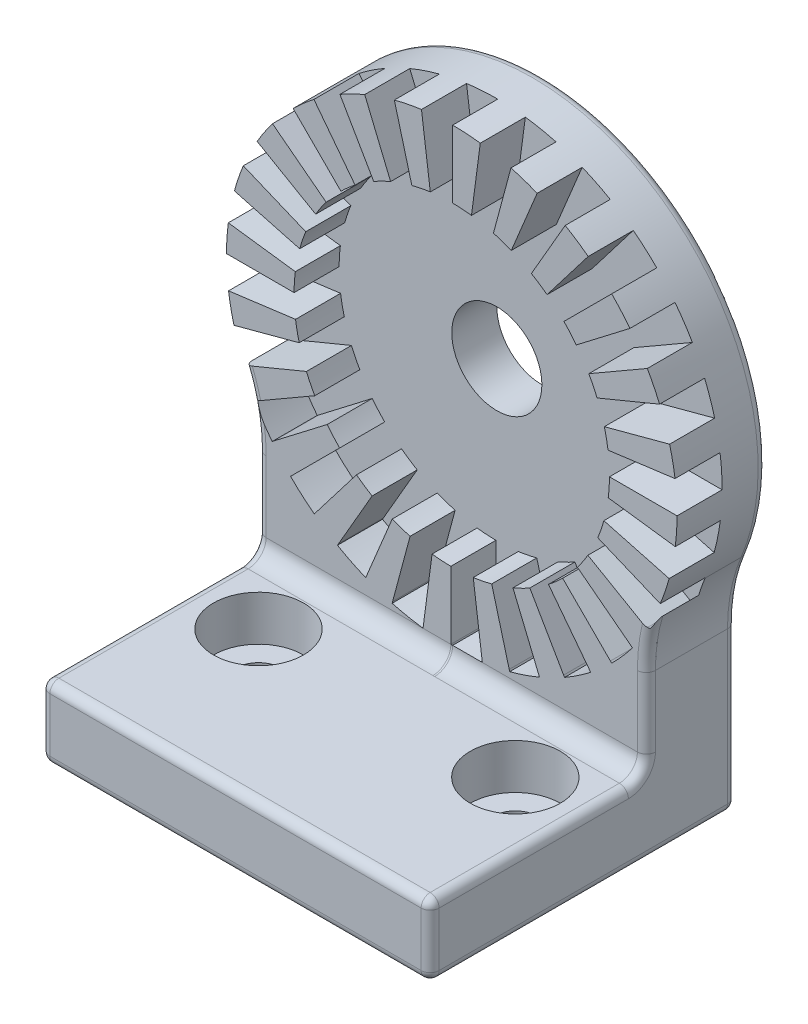
SolidWorks part; units mm, degrees
note: The reader was unsure of these and kept them because the rebuilt part matched: shared geometry of "Sketch1<3>", "Sketch2<3>".
ref_plane "Front Plane" through (0, 0, 0) normal (0, 0, 1) x (1, 0, 0)
ref_plane "Top Plane" through (0, 0, 0) normal (0, 1, 0) x (1, 0, 0)
ref_plane "Right Plane" through (0, 0, 0) normal (1, 0, 0) x (0, 0, -1)
sketch "Sketch1" plane through (0, 0, 0) normal (0, 0, 1) x (1, 0, 0)
  line L0 (0, 0) -> (0, 25) construction
  line L1 (0, 0) -> (3.2632, 24.7861) construction
  line L2 (0, 0) -> (6.4705, 24.1481) construction
  line L3 (0, 0) -> (9.5671, 23.097) construction
  line L4 (0, 0) -> (12.5, 21.6506) construction
  line L5 (0, 0) -> (15.219, 19.8338) construction
  line L6 (0, 0) -> (17.6777, 17.6777) construction
  line L7 (0, 0) -> (19.8338, 15.219) construction
  line L8 (0, 0) -> (21.6506, 12.5) construction
  line L9 (0, 0) -> (23.097, 9.5671) construction
  line L10 (0, 0) -> (24.1481, 6.4705) construction
  line L11 (0, 0) -> (24.7861, 3.2632) construction
  line L12 (0, 0) -> (25, 0) construction
  line L13 (0, 0) -> (24.7861, -3.2632) construction
  line L14 (0, 0) -> (24.1481, -6.4705) construction
  line L15 (0, 0) -> (23.097, -9.5671) construction
  line L16 (0, 0) -> (21.6506, -12.5) construction
  line L17 (0, 0) -> (19.8338, -15.219) construction
  line L18 (0, 0) -> (17.6777, -17.6777) construction
  line L19 (0, 0) -> (15.219, -19.8338) construction
  line L20 (0, 0) -> (12.5, -21.6506) construction
  line L21 (0, 0) -> (9.5671, -23.097) construction
  line L22 (0, 0) -> (6.4705, -24.1481) construction
  line L23 (0, 0) -> (3.2632, -24.7861) construction
  line L24 (0, 0) -> (0, -25) construction
  line L25 (0, 0) -> (-3.2632, -24.7861) construction
  line L26 (0, 0) -> (-6.4705, -24.1481) construction
  line L27 (0, 0) -> (-9.5671, -23.097) construction
  line L28 (0, 0) -> (-12.5, -21.6506) construction
  line L29 (0, 0) -> (-15.219, -19.8338) construction
  line L30 (0, 0) -> (-17.6777, -17.6777) construction
  line L31 (0, 0) -> (-19.8338, -15.219) construction
  line L32 (0, 0) -> (-21.6506, -12.5) construction
  line L33 (0, 0) -> (-23.097, -9.5671) construction
  line L34 (0, 0) -> (-24.1481, -6.4705) construction
  line L35 (0, 0) -> (-24.7861, -3.2632) construction
  line L36 (0, 0) -> (-25, 0) construction
  line L37 (0, 0) -> (-24.7861, 3.2632) construction
  line L38 (0, 0) -> (-24.1481, 6.4705) construction
  line L39 (0, 0) -> (-23.097, 9.5671) construction
  line L40 (0, 0) -> (-21.6506, 12.5) construction
  line L41 (0, 0) -> (-19.8338, 15.219) construction
  line L42 (0, 0) -> (-17.6777, 17.6777) construction
  line L43 (0, 0) -> (-15.219, 19.8338) construction
  line L44 (0, 0) -> (-12.5, 21.6506) construction
  line L45 (0, 0) -> (-9.5671, 23.097) construction
  line L46 (0, 0) -> (-6.4705, 24.1481) construction
  line L47 (0, 0) -> (-3.2632, 24.7861) construction
  line L48 (-1.5257, 0.1) -> (-24.7992, 3.164)
  line L49 (-1.5257, 0.1) -> (-25, 0.1)
  line L50 (-1.4478, 0.4915) -> (-23.1353, 9.4747)
  line L51 (-1.4478, 0.4915) -> (-24.1223, 6.5671)
  line L52 (-1.2713, 0.8495) -> (-19.8947, 15.1397)
  line L53 (-1.2713, 0.8495) -> (-21.6006, 12.5866)
  line L54 (-1.0081, 1.1495) -> (-15.2984, 19.773)
  line L55 (-1.0081, 1.1495) -> (-17.607, 17.7484)
  line L56 (-0.6763, 1.3713) -> (-9.6595, 23.0587)
  line L57 (-0.6763, 1.3713) -> (-12.4134, 21.7006)
  line L58 (-0.2983, 1.4996) -> (-3.3623, 24.7731)
  line L59 (-0.2983, 1.4996) -> (-6.3739, 24.174)
  line L60 (0.1, 1.5257) -> (3.164, 24.7992)
  line L61 (0.1, 1.5257) -> (0.1, 25)
  line L62 (0.4915, 1.4478) -> (9.4747, 23.1353)
  line L63 (0.4915, 1.4478) -> (6.5671, 24.1223)
  line L64 (0.8495, 1.2713) -> (15.1397, 19.8947)
  line L65 (0.8495, 1.2713) -> (12.5866, 21.6006)
  line L66 (1.1495, 1.0081) -> (19.773, 15.2984)
  line L67 (1.1495, 1.0081) -> (17.7484, 17.607)
  line L68 (1.3713, 0.6763) -> (23.0587, 9.6595)
  line L69 (1.3713, 0.6763) -> (21.7006, 12.4134)
  line L70 (1.4996, 0.2983) -> (24.7731, 3.3623)
  line L71 (1.4996, 0.2983) -> (24.174, 6.3739)
  line L72 (1.5257, -0.1) -> (24.7992, -3.164)
  line L73 (1.5257, -0.1) -> (25, -0.1)
  line L74 (1.4478, -0.4915) -> (23.1353, -9.4747)
  line L75 (1.4478, -0.4915) -> (24.1223, -6.5671)
  line L76 (1.2713, -0.8495) -> (19.8947, -15.1397)
  line L77 (1.2713, -0.8495) -> (21.6006, -12.5866)
  line L78 (1.0081, -1.1495) -> (15.2984, -19.773)
  line L79 (1.0081, -1.1495) -> (17.607, -17.7484)
  line L80 (0.6763, -1.3713) -> (9.6595, -23.0587)
  line L81 (0.6763, -1.3713) -> (12.4134, -21.7006)
  line L82 (0.2983, -1.4996) -> (3.3623, -24.7731)
  line L83 (0.2983, -1.4996) -> (6.3739, -24.174)
  line L84 (-0.1, -1.5257) -> (-3.164, -24.7992)
  line L85 (-0.1, -1.5257) -> (-0.1, -25)
  line L86 (-0.4915, -1.4478) -> (-9.4747, -23.1353)
  line L87 (-0.4915, -1.4478) -> (-6.5671, -24.1223)
  line L88 (-0.8495, -1.2713) -> (-15.1397, -19.8947)
  line L89 (-0.8495, -1.2713) -> (-12.5866, -21.6006)
  line L90 (-1.1495, -1.0081) -> (-19.773, -15.2984)
  line L91 (-1.1495, -1.0081) -> (-17.7484, -17.607)
  line L92 (-1.3713, -0.6763) -> (-23.0587, -9.6595)
  line L93 (-1.3713, -0.6763) -> (-21.7006, -12.4134)
  line L94 (-1.4996, -0.2983) -> (-24.7731, -3.3623)
  line L95 (-1.4996, -0.2983) -> (-24.174, -6.3739)
  circle A0 centre (0, 0) radius 25 construction
  arc A1 (-25, 0.1) -> (-24.7992, 3.164) centre (-1.5257, 0.1) cw
  arc A2 (-24.1223, 6.5671) -> (-23.1353, 9.4747) centre (-1.4478, 0.4915) cw
  arc A3 (-21.6006, 12.5866) -> (-19.8947, 15.1397) centre (-1.2713, 0.8495) cw
  arc A4 (-17.607, 17.7484) -> (-15.2984, 19.773) centre (-1.0081, 1.1495) cw
  arc A5 (-12.4134, 21.7006) -> (-9.6595, 23.0587) centre (-0.6763, 1.3713) cw
  arc A6 (-6.3739, 24.174) -> (-3.3623, 24.7731) centre (-0.2983, 1.4996) cw
  arc A7 (0.1, 25) -> (3.164, 24.7992) centre (0.1, 1.5257) cw
  arc A8 (6.5671, 24.1223) -> (9.4747, 23.1353) centre (0.4915, 1.4478) cw
  arc A9 (12.5866, 21.6006) -> (15.1397, 19.8947) centre (0.8495, 1.2713) cw
  arc A10 (17.7484, 17.607) -> (19.773, 15.2984) centre (1.1495, 1.0081) cw
  arc A11 (21.7006, 12.4134) -> (23.0587, 9.6595) centre (1.3713, 0.6763) cw
  arc A12 (24.174, 6.3739) -> (24.7731, 3.3623) centre (1.4996, 0.2983) cw
  arc A13 (25, -0.1) -> (24.7992, -3.164) centre (1.5257, -0.1) cw
  arc A14 (24.1223, -6.5671) -> (23.1353, -9.4747) centre (1.4478, -0.4915) cw
  arc A15 (21.6006, -12.5866) -> (19.8947, -15.1397) centre (1.2713, -0.8495) cw
  arc A16 (17.607, -17.7484) -> (15.2984, -19.773) centre (1.0081, -1.1495) cw
  arc A17 (12.4134, -21.7006) -> (9.6595, -23.0587) centre (0.6763, -1.3713) cw
  arc A18 (6.3739, -24.174) -> (3.3623, -24.7731) centre (0.2983, -1.4996) cw
  arc A19 (-0.1, -25) -> (-3.164, -24.7992) centre (-0.1, -1.5257) cw
  arc A20 (-6.5671, -24.1223) -> (-9.4747, -23.1353) centre (-0.4915, -1.4478) cw
  arc A21 (-12.5866, -21.6006) -> (-15.1397, -19.8947) centre (-0.8495, -1.2713) cw
  arc A22 (-17.7484, -17.607) -> (-19.773, -15.2984) centre (-1.1495, -1.0081) cw
  arc A23 (-21.7006, -12.4134) -> (-23.0587, -9.6595) centre (-1.3713, -0.6763) cw
  arc A24 (-24.174, -6.3739) -> (-24.7731, -3.3623) centre (-1.4996, -0.2983) cw
  circle A25 centre (0, 0) radius 25
  point P54 (0, 0)
  point P150 (0, 0)
  dimension "D1" = 50
  dimension "D4" = 24
  dimension "D5" = 50
  dimension "D2" = 48
  dimension "D3" = 0.1
extrude "Boss-Extrude1" add sketch "Sketch1" along normal blind 10 contours L48 A25 L49 | L50 A25 L51 | L52 A25 L53 | L54 A25 L55 | L56 A25 L57 | L58 A25 L59 | L60 A25 L61 | L62 A25 L63 | L64 A25 L65 | L66 A25 L67 | L68 A25 L69 | L70 A25 L71 | L72 A25 L73 | L74 A25 L75 | L76 A25 L77 | L78 A25 L79 | L80 A25 L81 | L82 A25 L83 | L86 A25 L87 | L88 A25 L89 | L90 A25 L91 | L92 A25 L93 | L94 A25 L95 | L84 A19 L85
extrude "Boss-Extrude2" add sketch "Sketch1<3>" along normal blind 5 contours A25
sketch "Sketch1<3>" plane through (0, 0, 0) normal (0, 0, 1) x (1, 0, 0) same geometry as "Sketch1"
sketch "Sketch2" plane through (0, 0, 0) normal (0, 0, 1) x (1, 0, 0)
  circle A0 centre (0, 0) radius 5
  circle A1 centre (0, 0) radius 17.5
  dimension "D1" = 10
  dimension "D2" = 35
extrude "Cut-Extrude1" cut sketch "Sketch2" along normal through all contours A0
extrude "Boss-Extrude3" add sketch "Sketch2<3>" along normal through all
sketch "Sketch2<3>" plane through (0, 0, 0) normal (0, 0, 1) x (1, 0, 0) same geometry as "Sketch2"
sketch "Sketch3" plane through (0, 0, 0) normal (0, 0, 1) x (1, 0, 0)
  line L0 (21.6005, -12.5865) -> (21.6005, -35)
  line L1 (21.6005, -35) -> (-21.6005, -35)
  line L2 (-21.6005, -35) -> (-21.6005, -12.5865)
  arc A1 (-24.799, 3.164) -> (-24.9998, 0.1) centre (0, 0) ccw construction
  arc A5 (-21.6005, -12.5865) -> (21.6005, -12.5865) centre (0, 0) ccw
  dimension "D1" = 10
extrude "Boss-Extrude4" add sketch "Sketch3" along normal blind 10 contours A5 L2 L1 L0
fillet "Fillet1" radius 20 2 edges at (21.6005, -12.5865, 2.5) (-21.6005, -12.5865, 2.5)
sketch "Sketch4" plane through (0, 0, 0) normal (0, 0, 1) x (1, 0, 0)
  line L0 (-22.1146, -12.6524) -> (-15.2052, -8.6633) construction
  line L1 (-21.6005, -35) -> (-21.6005, -12.5865) construction
  line L2 (-22.1146, -12.6524) -> (-21.7071, -12.4172)
  line L3 (-21.6005, -35) -> (-21.6005, -12.5865)
  line L4 (-21.7071, -12.4172) -> (-15.2052, -8.6633) construction
  arc A0 (-21.6005, -12.5865) -> (-19.7728, -15.2982) centre (0, 0) ccw construction
  arc A1 (-21.6005, -12.5865) -> (-19.7728, -15.2982) centre (0, 0) ccw construction
  arc A2 (-21.6005, -12.5865) -> (-21.7071, -12.4172) centre (-24.1024, -14.0444) ccw
  arc A3 (-21.6005, -17.1581) -> (-22.1146, -12.6524) centre (-41.6005, -17.1581) ccw construction
  arc A4 (-21.6005, -17.1581) -> (-22.1146, -12.6524) centre (-41.6005, -17.1581) ccw
extrude "Boss-Extrude5" add sketch "Sketch4" along normal blind 10 contours A4 L3 A2 L2
sketch "Sketch5" plane through (0, 0, 0) normal (0, 0, 1) x (1, 0, 0)
  line L0 (21.6005, -12.5865) -> (21.6005, -35) construction
  line L1 (21.6005, -12.5865) -> (21.6005, -17.1581)
  line L2 (21.6005, -17.1581) -> (21.6005, -35) construction
  arc A0 (23.1114, -9.5323) -> (21.6005, -17.1581) centre (41.6005, -17.1581) ccw construction
  arc A1 (23.1114, -9.5323) -> (21.6005, -17.1581) centre (41.6005, -17.1581) ccw
  arc A2 (23.1114, -9.5323) -> (21.6005, -12.5865) centre (0, 0) cw
extrude "Boss-Extrude6" add sketch "Sketch5" along normal blind 10
sketch "Sketch6" plane through (0, 0, 0) normal (0, 0, 1) x (1, 0, 0)
  line L0 (21.6005, -17.1581) -> (21.6005, -35) construction
  line L1 (-21.6005, -35) -> (21.6005, -35)
  line L2 (-21.6005, -35) -> (-21.6005, -26.9998)
  line L3 (-21.6005, -26.9998) -> (21.6005, -26.9998)
  line L4 (21.6005, -35) -> (21.6005, -26.9998)
  dimension "D1" = 2
extrude "Boss-Extrude7" add sketch "Sketch6" along normal blind 34
fillet "Fillet2" radius 2 1 edges at (0, -26.9998, 10)
fillet "Fillet3" radius 1 20 edges at (0, -35, 0) (0, -35, 34) (-21.9686, -13.3386, 10) (-21.6005, -21.079, 10) (-21.6005, -26.414, 10.5858) (21.9818, -13.2711, 10) (21.6005, -21.079, 10) (21.6005, -26.414, 10.5858) (-21.6005, -26.0791, 0) (-21.9818, -13.2711, 0) (0, 25, 0) (21.9818, -13.2711, 0) (-21.6005, -26.9998, 23) (21.6005, -26.9998, 23) (21.6005, -26.0791, 0) (21.6005, -30.9999, 34) (21.6005, -35, 17) (-21.6005, -35, 17) (-21.6005, -30.9999, 34) (0, -26.9998, 34)
sketch "Sketch7" plane through (0, -35, 0) normal (0, -1, 0) x (-1, 0, 0)
  circle A0 centre (14.25, -17.2) radius 2.5
  circle A1 centre (-14.25, -17.2) radius 2.5
  dimension "D1" = 5
  dimension "D2" = 5
extrude "Cut-Extrude2" cut sketch "Sketch7" against normal up to next
sketch "Sketch8" plane through (0, -35, 0) normal (0, -1, 0) x (-1, 0, 0)
  circle A0 centre (-14.25, -17.2) radius 5
  circle A1 centre (14.25, -17.2) radius 5
  dimension "D1" = 10
  dimension "D2" = 10
extrude "Cut-Extrude3" cut sketch "Sketch8" along normal blind 5 from surface at -8.0002 starting at face at (-14.25, -26.9998, 14.7)
sketch "Sketch9" plane through (0, 0, 10) normal (0, 0, 1) x (1, 0, 0)
  circle A0 centre (0, 0) radius 17.5
  dimension "D1" = 35
extrude "Cut-Extrude4" cut sketch "Sketch9" against normal blind 5
sketch "Sketch11" plane through (0, 0, 0) normal (0, 0, 1) x (1, 0, 0)
  line L0 (6.4248, -24.3672) -> (6.3738, -24.1738)
  line L1 (9.7367, -23.243) -> (9.6594, -23.0585)
  arc A1 (6.3738, -24.1738) -> (9.6594, -23.0585) centre (0, 0) ccw construction
  arc A2 (6.4248, -24.3672) -> (9.7367, -23.243) centre (0, 0) ccw
  arc A3 (6.4248, -24.3672) -> (9.7367, -23.243) centre (0, 0) ccw
  arc A4 (6.3738, -24.1738) -> (9.6594, -23.0585) centre (0, 0) ccw
  dimension "D1" = 0.2
extrude "Cut-Extrude7" cut sketch "Sketch11" against normal blind 5 from surface at 10 starting at face at (20.8225, 4.1418, 10)
pattern_circular "CirPattern1" count 24 over 360 about axis through (0, 0, 0) along (0, 0, 1) of "Cut-Extrude7"
